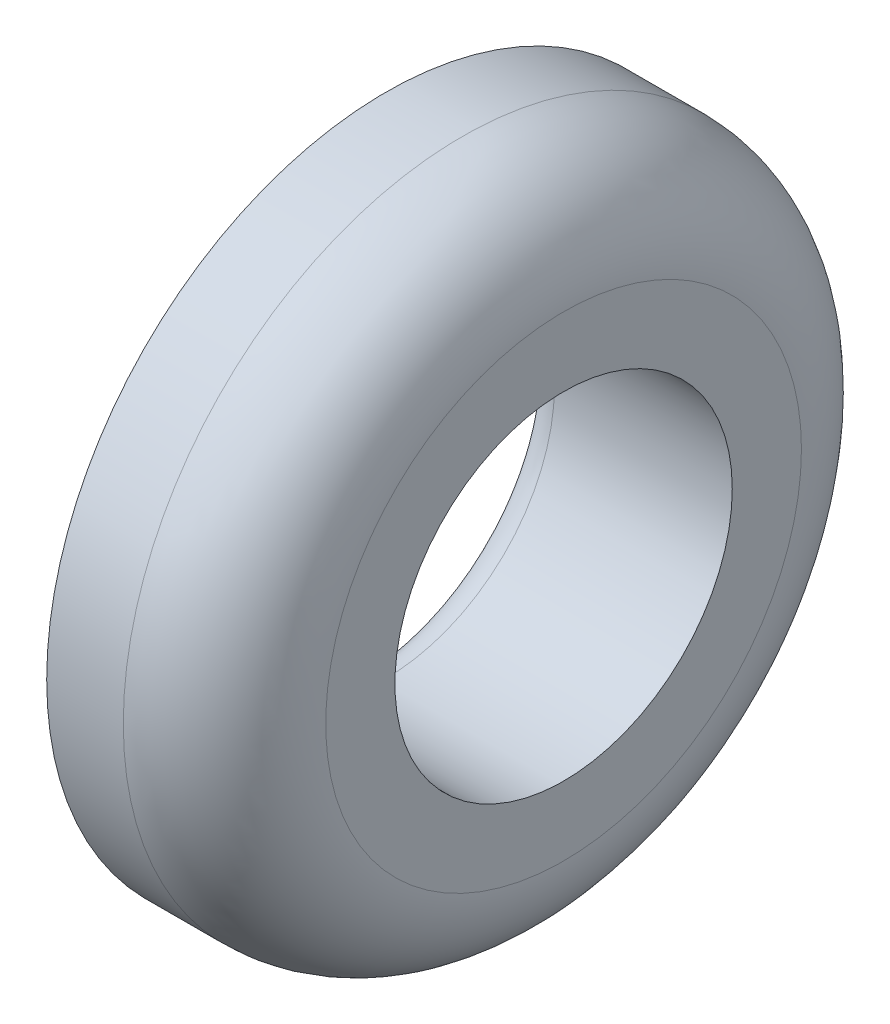
SolidWorks part; units mm, degrees
material "Rubber"
ref_plane "Front Plane" through (0, 0, 0) normal (0, 0, 1) x (1, 0, 0)
ref_plane "Top Plane" through (0, 0, 0) normal (0, 1, 0) x (1, 0, 0)
ref_plane "Right Plane" through (0, 0, 0) normal (1, 0, 0) x (0, 0, -1)
sketch "Sketch1" plane through (0, 0, 0) normal (1, 0, 0) x (0, 0, -1)
  circle A0 centre (0, 0) radius 12.7635
  circle A1 centre (0, 0) radius 6.35
extrude "Boss-Extrude1" add sketch "Sketch1" along normal blind 7.9629
fillet "Fillet1" radius 3.81 1 edges at (7.9629, 0, -12.7635)
sketch "Sketch2" plane through (0, 0, 0) normal (-1, 0, 0) x (0, 0, 1)
  circle A0 centre (0, 0) radius 11.8027
  circle A1 centre (0, 0) radius 12.7635
extrude "Cut-Extrude1" cut sketch "Sketch2" against normal blind 1.27
fillet "Fillet2" radius 1.27 2 edges at (0, 0, 11.8027) (0, 0, -6.35)
